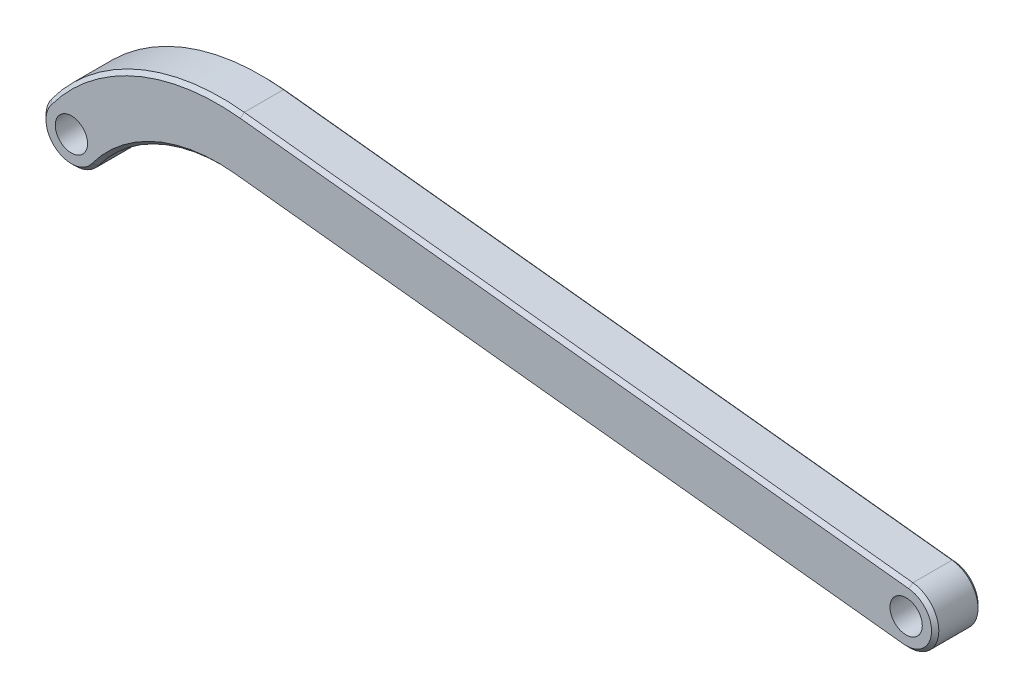
SolidWorks part; units mm, degrees
ref_plane "Front Plane" through (0, 0, 0) normal (0, 0, 1) x (1, 0, 0)
ref_plane "Top Plane" through (0, 0, 0) normal (0, 1, 0) x (1, 0, 0)
ref_plane "Right Plane" through (0, 0, 0) normal (1, 0, 0) x (0, 0, -1)
sketch "Sketch2" plane through (0, 0, 0) normal (0, 0, 1) x (1, 0, 0)
  line L0 (0, 0) -> (115, 0) construction
  line L1 (22.8811, 10.0726) -> (115, 0) construction
  line L2 (0, 0) -> (22.8811, 10.0726) construction
  line L3 (22.4463, 6.0963) -> (114.5652, -3.9763)
  line L4 (23.3158, 14.0489) -> (115.4348, 3.9763)
  arc A0 (0, 0) -> (22.8811, 10.0726) centre (20.1637, -14.7793) cw construction
  arc A1 (3.2262, -2.3647) -> (22.4463, 6.0963) centre (20.1637, -14.7793) cw
  arc A2 (-3.2262, 2.3647) -> (23.3158, 14.0489) centre (20.1637, -14.7793) cw
  arc A3 (-3.2262, 2.3647) -> (3.2262, -2.3647) centre (0, 0) ccw
  arc A4 (115.4348, 3.9763) -> (114.5652, -3.9763) centre (115, 0) cw
  circle A5 centre (0, 0) radius 2.225
  circle A6 centre (115, 0) radius 2.225
  dimension "D2" = 25
  dimension "D5" = 4.45
  dimension "D1" = 115
  dimension "D3" = 25
  dimension "D4" = 4
  dimension "D6" = 4
extrude "Boss-Extrude1" add sketch "Sketch2" along normal blind 6.4 contours A6 A5 region at (56.1052, 5.3761, 0)
chamfer "Chamfer1" distance 0.5 angle 45 12 edges at (11.7027, 4.4408, 0) (-2.3647, -3.2262, 0) (68.5057, 1.06, 0) (8.4794, 11.7628, 0) (118.9763, -0.4348, 0) (69.3753, 9.0126, 0) (11.7027, 4.4408, 6.4) (-2.3647, -3.2262, 6.4) (68.5057, 1.06, 6.4) (8.4794, 11.7628, 6.4) (118.9763, -0.4348, 6.4) (69.3753, 9.0126, 6.4)
